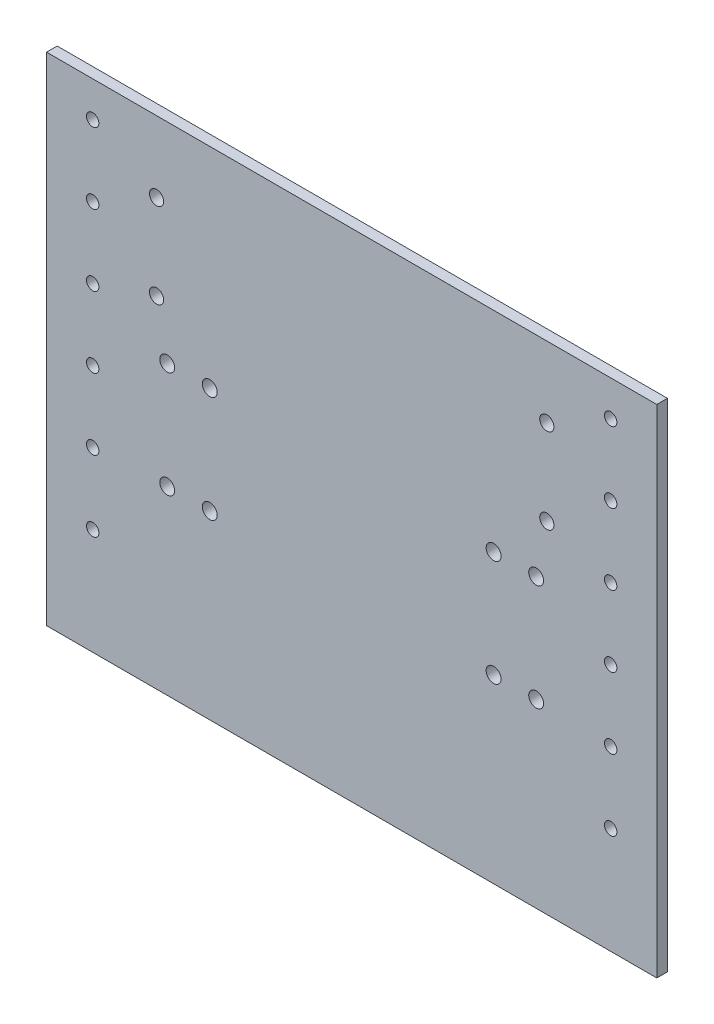
SolidWorks part; units mm, degrees
material "A-玻璃纤维"
ref_plane "前视基准面" through (0, 0, 0) normal (0, 0, 1) x (1, 0, 0)
ref_plane "上视基准面" through (0, 0, 0) normal (0, 1, 0) x (1, 0, 0)
ref_plane "右视基准面" through (0, 0, 0) normal (1, 0, 0) x (0, 0, -1)
other "Configuration Table"
sketch "草图1" plane through (0, 0, 0) normal (0, 0, 1) x (1, 0, 0)
  line L1 (0, 0) -> (172, 0)
  line L2 (0, 0) -> (0, -140)
  line L3 (0, -140) -> (172, -140)
  line L4 (172, 0) -> (172, -140)
  dimension "D1" = 172
  dimension "D2" = 140
extrude "凸台-拉伸1" add sketch "草图1" along normal blind 3
sketch "草图2" plane through (0, 0, 3) normal (0, 0, 1) x (1, 0, 0)
  line L0 (86, 0) -> (86, -183.257) construction
  line L1 (172, 0) -> (0, 0) construction
  circle A0 centre (31, -20) radius 2
  circle A1 centre (31, -44) radius 2
  circle A2 centre (141, -44) radius 2
  circle A3 centre (141, -20) radius 2
  dimension "D1" = 4
  dimension "D2" = 2
  dimension "D3" = 24
  dimension "D4" = 55
  dimension "D5" = 20
extrude "切除-拉伸1" cut sketch "草图2" against normal blind 37
sketch "草图3" plane through (0, 0, 3) normal (0, 0, 1) x (1, 0, 0)
  line L1 (86, 0) -> (86, -206.5924) construction
  line L2 (172, 0) -> (0, 0) construction
  circle A0 centre (34, -59) radius 2.1
  circle A1 centre (46, -59) radius 2.1
  circle A2 centre (34, -89) radius 2.1
  circle A3 centre (46, -89) radius 2.1
  circle A4 centre (126, -89) radius 2.1
  circle A5 centre (138, -89) radius 2.1
  circle A6 centre (126, -59) radius 2.1
  circle A7 centre (138, -59) radius 2.1
  circle A8 centre (31, -44) radius 2 construction
  dimension "D1" = 4.2
  dimension "D3" = 12
  dimension "D5" = 30
  dimension "D6" = 40
  dimension "D7" = 15
  dimension "D2" = 2
  dimension "D4" = 2
extrude "切除-拉伸2" cut sketch "草图3" against normal blind 10
sketch "草图4" plane through (0, 0, 3) normal (0, 0, 1) x (1, 0, 0)
  line L0 (0, 0) -> (0, -140) construction
  line L1 (86, 0) -> (86, -140) construction
  line L2 (172, 0) -> (0, 0) construction
  line L3 (0, -140) -> (172, -140) construction
  circle A0 centre (13, -10) radius 1.75
  circle A1 centre (13, -30) radius 1.75
  circle A2 centre (13, -50) radius 1.75
  circle A3 centre (13, -70) radius 1.75
  circle A4 centre (13, -90) radius 1.75
  circle A5 centre (13, -110) radius 1.75
  circle A6 centre (159, -110) radius 1.75
  circle A7 centre (159, -90) radius 1.75
  circle A8 centre (159, -70) radius 1.75
  circle A9 centre (159, -50) radius 1.75
  circle A10 centre (159, -30) radius 1.75
  circle A11 centre (159, -10) radius 1.75
  dimension "D1" = 3.5
  dimension "D2" = 13
  dimension "D4" = 10
  dimension "D5" = 20
  dimension "D3" = 6
extrude "切除-拉伸3" cut sketch "草图4" against normal blind 10
